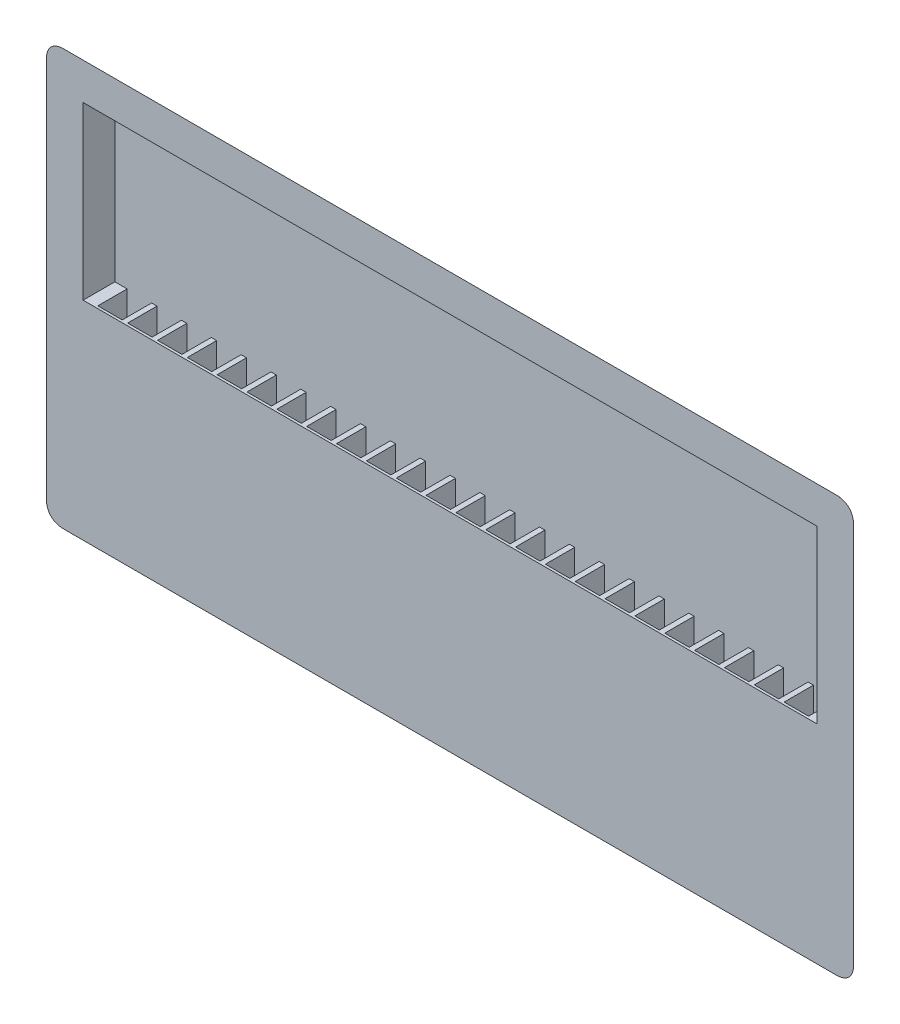
SolidWorks part; units mm, degrees
material "ABS"
ref_plane "Płaszczyzna XY" through (0, 0, 0) normal (0, 0, 1) x (1, 0, 0)
ref_plane "Płaszczyzna XZ" through (0, 0, 0) normal (0, 1, 0) x (1, 0, 0)
ref_plane "Płaszczyzna YZ" through (0, 0, 0) normal (1, 0, 0) x (0, 0, -1)
sketch "Szkic1" plane through (0, 0, 0) normal (0, 0, 1) x (1, 0, 0)
  line L1 (-150, -70) -> (150, -70)
  line L2 (-150, -70) -> (-150, 70)
  line L3 (-150, 70) -> (150, 70)
  line L4 (150, -70) -> (150, 70)
  line L5 (-150, -70) -> (150, 70) construction
  line L6 (-150, 70) -> (150, -70) construction
  point P0 (0, 0)
  dimension "D1" = 300
  dimension "D2" = 140
extrude "Dodanie-wyciągnięcie1" add sketch "Szkic1" along normal blind 15 draft 45 draft outward yes
ref_plane "Płaszczyzna1" through (0, 0, 2) normal (0, 0, -1) x (-1, 0, 0)
sketch "Szkic2" plane through (0, 0, 2) normal (0, 0, -1) x (-1, 0, 0)
  line L5 (-150, -70) -> (150, 70) construction
  line L6 (-150, 70) -> (150, -70) construction
  line L7 (-150, -70) -> (-150, 70) construction
  line L8 (150, 70) -> (-150, 70)
  line L9 (150, 70) -> (150, 0)
  line L10 (150, 0) -> (-150, 0)
  line L11 (-150, 70) -> (-150, 0)
  point P0 (0, 0)
extrude "Wytnij-wyciągnięcie1" cut sketch "Szkic2" against normal blind 15
sketch "Szkic3" plane through (0, 0, 0) normal (0, 1, 0) x (1, 0, 0)
  line L0 (150, -2) -> (-150, -2) construction
  line L1 (-145, -2) -> (-135, -2)
  line L2 (-145, -2) -> (-145, -14)
  line L3 (-145, -14) -> (-135, -14)
  line L4 (-135, -2) -> (-135, -14)
  line L5 (-150, -15) -> (-150, -2) construction
  line L6 (-132.8, -2) -> (-122.8, -2)
  line L7 (-132.8, -2) -> (-132.8, -14)
  line L8 (-132.8, -14) -> (-122.8, -14)
  line L9 (-122.8, -2) -> (-122.8, -14)
  line L10 (-120.6, -2) -> (-110.6, -2)
  line L11 (-120.6, -2) -> (-120.6, -14)
  line L12 (-120.6, -14) -> (-110.6, -14)
  line L13 (-110.6, -2) -> (-110.6, -14)
  line L14 (-108.4, -2) -> (-98.4, -2)
  line L15 (-108.4, -2) -> (-108.4, -14)
  line L16 (-108.4, -14) -> (-98.4, -14)
  line L17 (-98.4, -2) -> (-98.4, -14)
  line L18 (-96.2, -2) -> (-86.2, -2)
  line L19 (-96.2, -2) -> (-96.2, -14)
  line L20 (-96.2, -14) -> (-86.2, -14)
  line L21 (-86.2, -2) -> (-86.2, -14)
  line L22 (-84, -2) -> (-74, -2)
  line L23 (-84, -2) -> (-84, -14)
  line L24 (-84, -14) -> (-74, -14)
  line L25 (-74, -2) -> (-74, -14)
  line L26 (-71.8, -2) -> (-61.8, -2)
  line L27 (-71.8, -2) -> (-71.8, -14)
  line L28 (-71.8, -14) -> (-61.8, -14)
  line L29 (-61.8, -2) -> (-61.8, -14)
  line L30 (-59.6, -2) -> (-49.6, -2)
  line L31 (-59.6, -2) -> (-59.6, -14)
  line L32 (-59.6, -14) -> (-49.6, -14)
  line L33 (-49.6, -2) -> (-49.6, -14)
  line L34 (-47.4, -2) -> (-37.4, -2)
  line L35 (-47.4, -2) -> (-47.4, -14)
  line L36 (-47.4, -14) -> (-37.4, -14)
  line L37 (-37.4, -2) -> (-37.4, -14)
  line L38 (-35.2, -2) -> (-25.2, -2)
  line L39 (-35.2, -2) -> (-35.2, -14)
  line L40 (-35.2, -14) -> (-25.2, -14)
  line L41 (-25.2, -2) -> (-25.2, -14)
  line L42 (-23, -2) -> (-13, -2)
  line L43 (-23, -2) -> (-23, -14)
  line L44 (-23, -14) -> (-13, -14)
  line L45 (-13, -2) -> (-13, -14)
  line L46 (-10.8, -2) -> (-0.8, -2)
  line L47 (-10.8, -2) -> (-10.8, -14)
  line L48 (-10.8, -14) -> (-0.8, -14)
  line L49 (-0.8, -2) -> (-0.8, -14)
  line L50 (1.4, -2) -> (11.4, -2)
  line L51 (1.4, -2) -> (1.4, -14)
  line L52 (1.4, -14) -> (11.4, -14)
  line L53 (11.4, -2) -> (11.4, -14)
  line L54 (13.6, -2) -> (23.6, -2)
  line L55 (13.6, -2) -> (13.6, -14)
  line L56 (13.6, -14) -> (23.6, -14)
  line L57 (23.6, -2) -> (23.6, -14)
  line L58 (25.8, -2) -> (35.8, -2)
  line L59 (25.8, -2) -> (25.8, -14)
  line L60 (25.8, -14) -> (35.8, -14)
  line L61 (35.8, -2) -> (35.8, -14)
  line L62 (38, -2) -> (48, -2)
  line L63 (38, -2) -> (38, -14)
  line L64 (38, -14) -> (48, -14)
  line L65 (48, -2) -> (48, -14)
  line L66 (50.2, -2) -> (60.2, -2)
  line L67 (50.2, -2) -> (50.2, -14)
  line L68 (50.2, -14) -> (60.2, -14)
  line L69 (60.2, -2) -> (60.2, -14)
  line L70 (62.4, -2) -> (72.4, -2)
  line L71 (62.4, -2) -> (62.4, -14)
  line L72 (62.4, -14) -> (72.4, -14)
  line L73 (72.4, -2) -> (72.4, -14)
  line L74 (74.6, -2) -> (84.6, -2)
  line L75 (74.6, -2) -> (74.6, -14)
  line L76 (74.6, -14) -> (84.6, -14)
  line L77 (84.6, -2) -> (84.6, -14)
  line L78 (86.8, -2) -> (96.8, -2)
  line L79 (86.8, -2) -> (86.8, -14)
  line L80 (86.8, -14) -> (96.8, -14)
  line L81 (96.8, -2) -> (96.8, -14)
  line L82 (99, -2) -> (109, -2)
  line L83 (99, -2) -> (99, -14)
  line L84 (99, -14) -> (109, -14)
  line L85 (109, -2) -> (109, -14)
  line L86 (111.2, -2) -> (121.2, -2)
  line L87 (111.2, -2) -> (111.2, -14)
  line L88 (111.2, -14) -> (121.2, -14)
  line L89 (121.2, -2) -> (121.2, -14)
  line L90 (123.4, -2) -> (133.4, -2)
  line L91 (123.4, -2) -> (123.4, -14)
  line L92 (123.4, -14) -> (133.4, -14)
  line L93 (133.4, -2) -> (133.4, -14)
  line L94 (135.6, -2) -> (145.6, -2)
  line L95 (135.6, -2) -> (135.6, -14)
  line L96 (135.6, -14) -> (145.6, -14)
  line L97 (145.6, -2) -> (145.6, -14)
  dimension "D1" = 10
  dimension "D2" = 12
  dimension "D3" = 5
  dimension "D5" = 2.2
  dimension "D4" = 24
extrude "Wytnij-wyciągnięcie2" cut sketch "Szkic3" against normal blind 108
fillet "Zaokrąglenie1" radius 10 7 edges at (-157.5, -77.5, 7.5) (-157.5, 77.5, 7.5) (157.5, 77.5, 7.5) (157.5, -77.5, 7.5) (150, 0, 0) (0, 70, 0) (-150, 0, 0)
